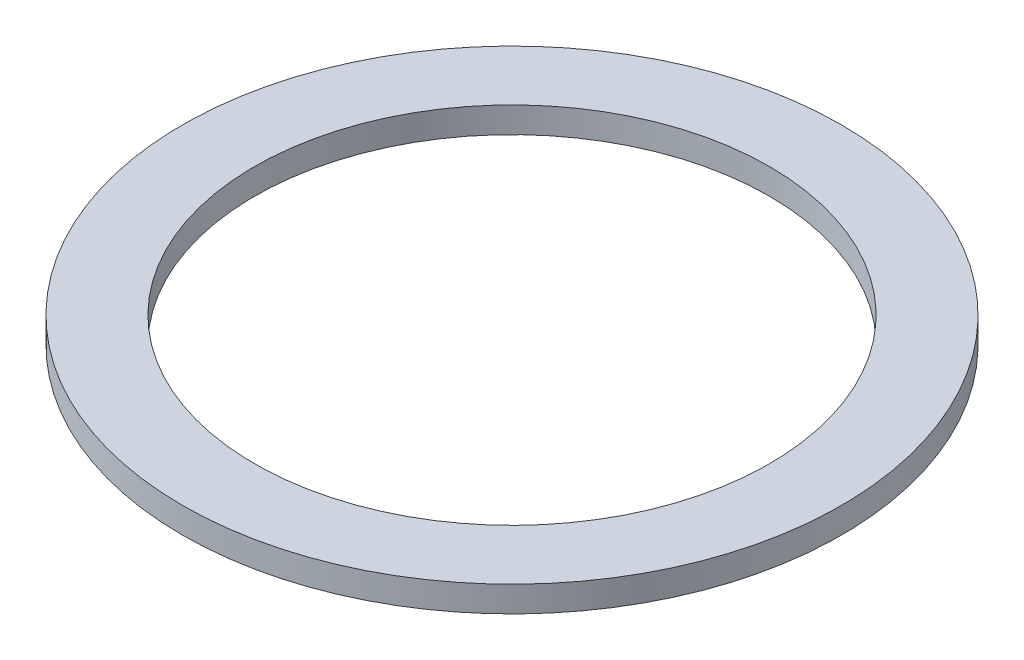
SolidWorks part; units mm, degrees
material "HYPALON"
ref_plane "Front Plane" through (0, 0, 0) normal (0, 0, 1) x (1, 0, 0)
ref_plane "Top Plane" through (0, 0, 0) normal (0, 1, 0) x (1, 0, 0)
ref_plane "Right Plane" through (0, 0, 0) normal (1, 0, 0) x (0, 0, -1)
sketch "Szkic1" plane through (0, 0, 0) normal (0, 0, 1) x (1, 0, 0)
  line L0 (0, 0) -> (-64, 0)
  line L1 (-64, 0) -> (-64, 5)
  line L2 (-64, 5) -> (-50, 5)
  line L3 (-50, 5) -> (-50, 0)
  line L4 (0, 0) -> (0, 23.5461)
  dimension "D1" = 64
  dimension "D2" = 5
  dimension "D3" = 50
revolve "Obrót1" add sketch "Szkic1" angle 360 about L4 region at (-57, 2.5, 0)
